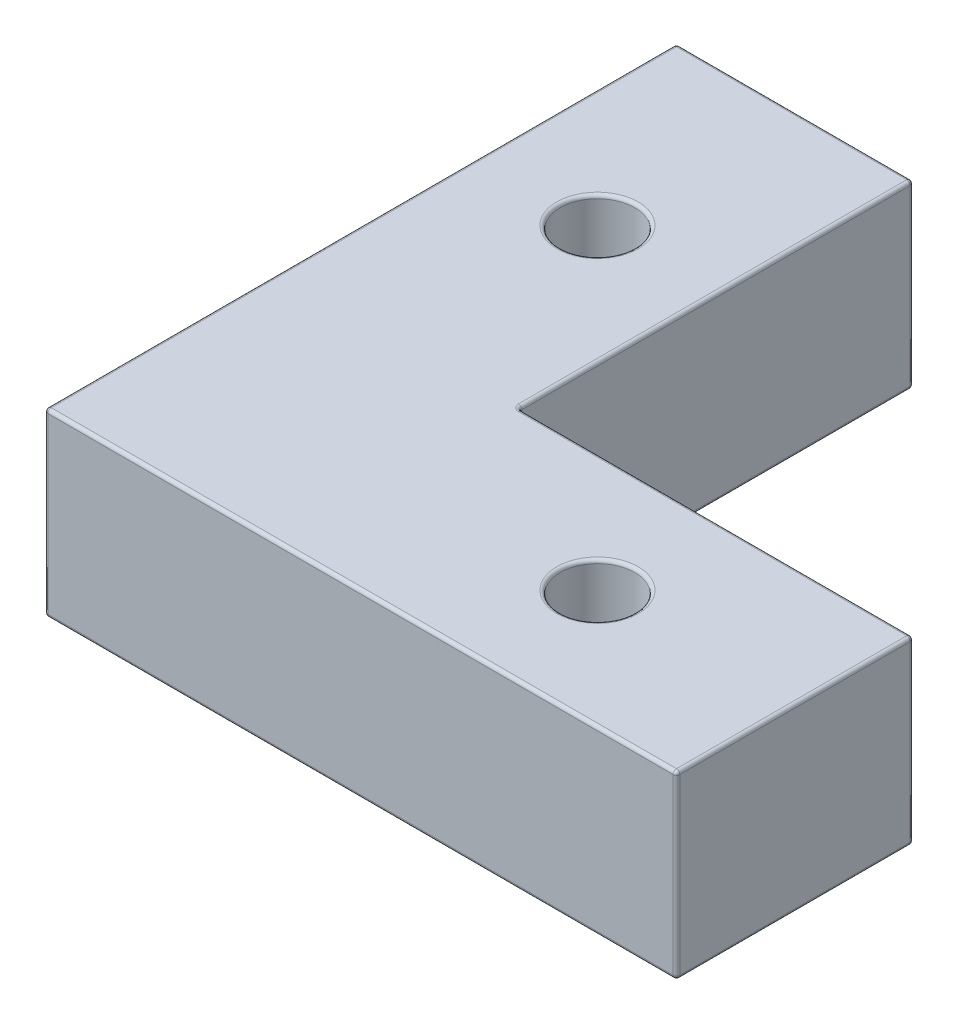
SolidWorks part; units mm, degrees
ref_plane "Front" through (0, 0, 0) normal (0, 0, 1) x (1, 0, 0)
ref_plane "Top" through (0, 0, 0) normal (0, 1, 0) x (1, 0, 0)
ref_plane "Right" through (0, 0, 0) normal (1, 0, 0) x (0, 0, -1)
sketch "Sketch1" plane through (0, 0, 0) normal (0, 1, 0) x (1, 0, 0)
  line L0 (0, 0) -> (24.0176, 24.0176) construction
  line L1 (0, 0) -> (13.335, 0)
  line L2 (0, 0) -> (0, 35.56)
  line L3 (0, 35.56) -> (13.335, 35.56)
  line L4 (13.335, 0) -> (13.335, 35.56)
  line L5 (0, 0) -> (35.56, 0)
  line L6 (0, 0) -> (0, 13.335)
  line L7 (0, 13.335) -> (35.56, 13.335)
  line L8 (35.56, 0) -> (35.56, 13.335)
  line L9 (1.524, 1.524) -> (1.524, 34.036)
  line L10 (1.524, 34.036) -> (11.811, 34.036)
  line L11 (11.811, 1.524) -> (11.811, 34.036)
  line L12 (1.524, 1.524) -> (11.811, 1.524)
  line L13 (1.524, 1.524) -> (1.524, 11.811)
  line L14 (1.524, 11.811) -> (34.036, 11.811)
  line L15 (34.036, 1.524) -> (34.036, 11.811)
  line L16 (1.524, 1.524) -> (34.036, 1.524)
  circle A0 centre (6.6675, 24.4475) radius 2.1
  circle A1 centre (24.4475, 6.6675) radius 2.1
  dimension "D8" = 4.2
  dimension "D1" = 13.335
  dimension "D2" = 35.56
  dimension "D3" = 35.56
  dimension "D4" = 13.335
  dimension "D5" = 6.6675
  dimension "D6" = 24.4475
  dimension "D7" = 1.524
extrude "Boss-Extrude1" add sketch "Sketch1" along normal blind 5.08 contours L16 L4 L5 L8 L7 L14 L15 | L11 L7 L4 L3 L2 L9 L10 | L7 L11 L10 L9 A0 | L0 L12 L11 | L9 L0 L14 | L4 L16 L15 L14 A1 | L11 L0 L7 | L0 L14 L4 | L9 L14 L11 L7 | L11 L16 L4 L14 | L2 L0 L9 L7 | L0 L1 L4 L16 L12 region at (0.7466, 0, -7.0408) region at (7.0408, 0, -0.7466) region at (4.953, 0, -8.382) region at (8.382, 0, -4.953) region at (13.5942, 0, -0.762) region at (0.2592, 0, -24.4475) region at (12.319, 0, -12.827) region at (12.573, 0, -6.6675) region at (6.6675, 0, -12.573) region at (12.827, 0, -12.319) region at (13.5662, 0, -6.6675) region at (1.7552, 0, -23.6855)
extrude "Boss-Extrude2" add sketch "Sketch1<3>" against normal blind 5.08 contours L16 L4 L5 L8 L7 L14 L15 | L0 L1 L4 L16 L12 | L2 L0 L9 L7 | L11 L7 L4 L3 L2 L9 L10 | L0 L14 L4 | L11 L0 L7 region at (0.7466, 0, -7.0408) region at (7.0408, 0, -0.7466) region at (13.5942, 0, -0.762) region at (0.2592, 0, -24.4475) region at (12.319, 0, -12.827) region at (12.827, 0, -12.319)
sketch "Sketch1<3>" plane through (0, 0, 0) normal (0, 1, 0) x (1, 0, 0) same geometry as "Sketch1"
fillet "Fillet1" radius 0.1905 26 edges at (6.6675, 5.08, -22.3475) (24.4475, 5.08, -4.5675) (6.6675, 5.08, -35.56) (13.335, 5.08, -24.4475) (13.335, 0, -35.56) (24.4475, 5.08, -13.335) (13.335, 0, -13.335) (35.56, 5.08, -6.6675) (35.56, 0, -13.335) (17.78, 5.08, 0) (35.56, 0, 0) (0, 5.08, -17.78) (0, 0, 0) (0, 0, -35.56) (0, -5.08, -17.78) (17.78, -5.08, 0) (35.56, -5.08, -6.6675) (24.4475, -5.08, -13.335) (13.335, -5.08, -24.4475) (6.6675, -5.08, -35.56) (6.6675, -5.08, -34.036) (11.811, -5.08, -22.9235) (22.9235, -5.08, -11.811) (34.036, -5.08, -6.6675) (17.78, -5.08, -1.524) (1.524, -5.08, -17.78)
